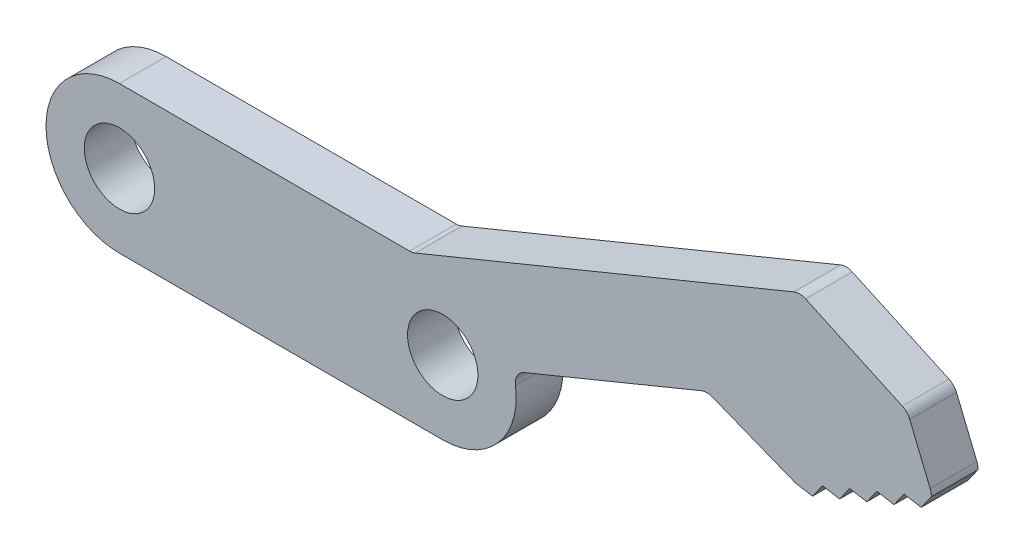
SolidWorks part; units mm, degrees
ref_plane "Front Plane" through (0, 0, 0) normal (0, 0, 1) x (1, 0, 0)
ref_plane "Top Plane" through (0, 0, 0) normal (0, 1, 0) x (1, 0, 0)
ref_plane "Right Plane" through (0, 0, 0) normal (1, 0, 0) x (0, 0, -1)
sketch "Sketch1" plane through (0, 0, 0) normal (0, 0, 1) x (1, 0, 0)
  line L0 (0, 0) -> (22, 0) construction
  line L1 (0, 5) -> (22, 5)
  line L2 (0, -5) -> (22, -5)
  line L3 (19.9443, 5) -> (23.9013, -4.6244) construction
  line L4 (19.9443, 5) -> (51.3901, 17.929)
  line L5 (23.9013, -4.6244) -> (55.3472, 8.3046) construction
  line L6 (51.3901, 17.929) -> (55.3472, 8.3046)
  line L7 (26.7913, 1.4293) -> (39.9788, 6.8514)
  line L8 (39.9788, 6.8514) -> (45.9998, 4.4614)
  line L9 (45.9998, 4.4614) -> (47.1642, 4.259)
  line L10 (47.1642, 4.259) -> (47.8495, 5.2219)
  line L11 (46.3033, 15.8375) -> (53.636, 12.4665)
  line L12 (55.608, 7.7306) -> (26.1494, -4.3813) construction
  line L13 (53.636, 12.4665) -> (39.9788, 6.8514) construction
  line L14 (49.014, 5.0195) -> (49.6993, 5.9824)
  line L15 (47.8495, 5.2219) -> (49.014, 5.0195)
  line L16 (50.8637, 5.78) -> (51.5491, 6.743)
  line L17 (49.6993, 5.9824) -> (50.8637, 5.78)
  line L18 (52.7135, 6.5406) -> (53.3988, 7.5035)
  line L19 (51.5491, 6.743) -> (52.7135, 6.5406)
  line L20 (54.5633, 7.3011) -> (55.2486, 8.264)
  line L21 (53.3988, 7.5035) -> (54.5633, 7.3011)
  line L22 (55.3472, 8.3046) -> (55.2486, 8.264)
  arc A0 (0, 5) -> (0, -5) centre (0, 0) ccw
  arc A1 (22, -5) -> (22, 5) centre (22, 0) ccw
  circle A2 centre (0, 0) radius 2.395
  circle A3 centre (22, 0) radius 2.395
  point P3 (11, 0)
  dimension "D3" = 4.79
  dimension "D1" = 10
  dimension "D2" = 22
  dimension "D4" = 157.65
  dimension "D5" = 34
  dimension "D6" = 14.24
  dimension "D7" = 4.5
  dimension "D8" = 136
  dimension "D9" = 0.63
  dimension "D10" = 2
  dimension "D11" = 5.5
  dimension "D12" = 5
extrude "Boss-Extrude1" add sketch "Sketch1" along normal blind 3.18 contours A1 L7 L8 L9 L10 L15 L14 L17 L16 L19 L18 L21 L20 L22 L6 L11 L4 L1 | A1 L1 A0 L2 A3 A2 region at (11, 0, 0) region at (40.3467, 8.6765, 0)
fillet "Fillet1" radius 1 6 edges at (39.9788, 6.8514, 1.59) (26.7913, 1.4293, 1.59) (19.9443, 5, 1.59) (46.3033, 15.8375, 1.59) (53.636, 12.4665, 1.59) (55.3472, 8.3046, 1.59)
